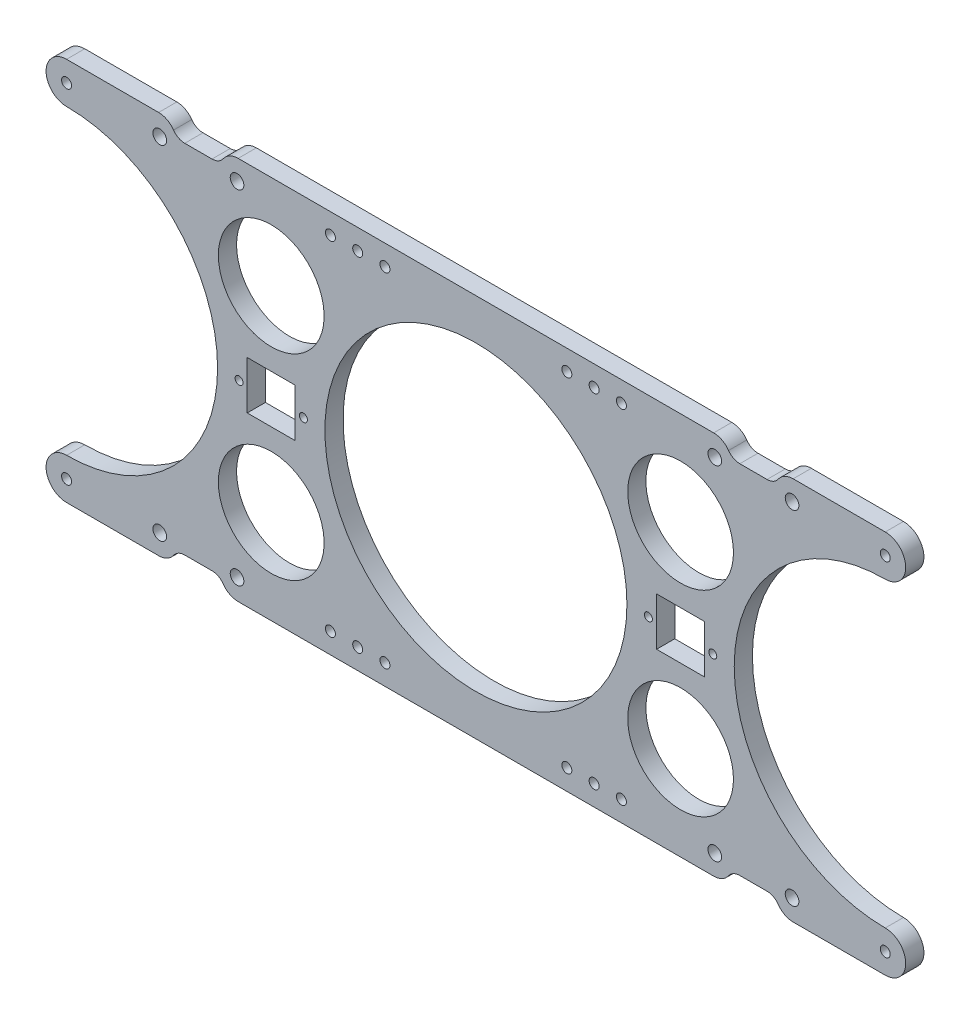
SolidWorks part; units mm, degrees
material "1060 Alloy"
ref_plane "Front Plane" through (0, 0, 0) normal (0, 0, 1) x (1, 0, 0)
ref_plane "Top Plane" through (0, 0, 0) normal (0, 1, 0) x (1, 0, 0)
ref_plane "Right Plane" through (0, 0, 0) normal (1, 0, 0) x (0, 0, -1)
sketch "Sketch1" plane through (0, 0, 0) normal (0, 0, 1) x (1, 0, 0)
  line L0 (0, 0) -> (225.1042, 0) construction
  line L1 (112.5521, -53.975) -> (112.5521, 53.975) construction
  line L2 (0, 83.05) -> (225.1042, 83.05) construction
  line L3 (225.1042, 83.05) -> (225.1042, -83.05) construction
  line L4 (-225.1042, 105.55) -> (-167.6042, 105.55)
  line L5 (-225.1042, -105.55) -> (-167.6042, -105.55)
  line L6 (0, 83.05) -> (0, 0) construction
  line L7 (-99.3521, -13.2) -> (-99.3521, 13.2)
  line L8 (99.3521, -13.2) -> (125.7521, -13.2)
  line L9 (99.3521, -13.2) -> (99.3521, 13.2)
  line L10 (99.3521, 13.2) -> (125.7521, 13.2)
  line L11 (125.7521, -13.2) -> (125.7521, 13.2)
  line L12 (99.3521, -13.2) -> (125.7521, 13.2) construction
  line L13 (99.3521, 13.2) -> (125.7521, -13.2) construction
  line L14 (-99.3521, 13.2) -> (-125.7521, 13.2)
  line L15 (-125.7521, -13.2) -> (-125.7521, 13.2)
  line L16 (-99.3521, -13.2) -> (-125.7521, -13.2)
  line L17 (0, 83.05) -> (0, 98.05) construction
  line L18 (50, 94.3) -> (80, 94.3) construction
  line L19 (80, 94.3) -> (94.2894, 76.5986) construction
  line L20 (225.1042, 0) -> (148.4177, 105.55) construction
  line L21 (225.1042, 0) -> (148.4177, -105.55) construction
  line L38 (-236.3542, 105.55) -> (-236.3542, -105.55) construction
  line L39 (-236.3542, -105.55) -> (-167.6042, -105.55) construction
  line L40 (236.3542, -105.55) -> (236.3542, 105.55) construction
  line L41 (236.3542, 105.55) -> (167.6042, 105.55) construction
  line L42 (-160.1042, 98.05) -> (-145.1042, 98.05)
  line L44 (-152.6042, 98.05) -> (-152.6042, 105.55) construction
  line L45 (-137.6042, 105.55) -> (137.6042, 105.55)
  line L46 (-167.6042, 105.55) -> (-236.3542, 105.55) construction
  line L47 (-160.1042, -98.05) -> (-145.1042, -98.05)
  line L48 (160.1042, -98.05) -> (145.1042, -98.05)
  line L49 (160.1042, 98.05) -> (145.1042, 98.05)
  line L50 (-137.6042, -105.55) -> (137.6042, -105.55) construction
  line L51 (-137.6042, -105.55) -> (137.6042, -105.55)
  line L52 (167.6042, -105.55) -> (225.1042, -105.55)
  line L53 (167.6042, -105.55) -> (236.3542, -105.55) construction
  line L54 (137.6042, 105.55) -> (-137.6042, 105.55) construction
  line L55 (167.6042, 105.55) -> (225.1042, 105.55)
  circle A0 centre (0, 0) radius 83.05
  arc A1 (225.1042, 83.05) -> (225.1042, -83.05) centre (225.1042, 0) ccw
  circle A2 centre (112.5521, 53.975) radius 29.075
  circle A3 centre (112.5521, -53.975) radius 29.075
  arc A4 (225.1042, 83.05) -> (225.1042, 105.55) centre (225.1042, 94.3) ccw
  arc A5 (225.1042, -83.05) -> (225.1042, -105.55) centre (225.1042, -94.3) cw
  circle A6 centre (-112.5521, -53.975) radius 29.075
  arc A7 (-225.1042, -83.05) -> (-225.1042, -105.55) centre (-225.1042, -94.3) ccw
  arc A8 (-225.1042, 83.05) -> (-225.1042, 105.55) centre (-225.1042, 94.3) cw
  circle A9 centre (-112.5521, 53.975) radius 29.075
  arc A10 (-225.1042, 83.05) -> (-225.1042, -83.05) centre (-225.1042, 0) cw
  circle A11 centre (225.1042, 0) radius 94.3 construction
  circle A13 centre (-195.1042, 94.3) radius 2.75 construction
  circle A31 centre (94.8521, 0) radius 2.2
  circle A32 centre (130.2521, 0) radius 2.2
  circle A33 centre (-130.2521, 0) radius 2.2
  circle A34 centre (-94.8521, 0) radius 2.2
  circle A35 centre (130.2521, 0) radius 3.175 construction
  circle A36 centre (225.1042, 0) radius 88.9 construction
  arc A37 (-167.6042, 105.55) -> (-160.1042, 98.05) centre (-160.1042, 105.55) ccw
  arc A38 (-145.1042, 98.05) -> (-137.6042, 105.55) centre (-145.1042, 105.55) ccw
  circle A39 centre (-195.1042, 94.3) radius 7.5 construction
  circle A40 centre (-173.8542, 94.3) radius 3.75
  circle A42 centre (-131.3542, 94.3) radius 3.75
  arc A43 (-145.1042, -98.05) -> (-137.6042, -105.55) centre (-145.1042, -105.55) cw
  arc A44 (-167.6042, -105.55) -> (-160.1042, -98.05) centre (-160.1042, -105.55) cw
  circle A45 centre (-131.3542, -94.3) radius 3.75
  circle A46 centre (-173.8542, -94.3) radius 3.75
  circle A47 centre (131.3542, -94.3) radius 3.75
  arc A48 (145.1042, -98.05) -> (137.6042, -105.55) centre (145.1042, -105.55) ccw
  arc A49 (167.6042, -105.55) -> (160.1042, -98.05) centre (160.1042, -105.55) ccw
  circle A50 centre (173.8542, -94.3) radius 3.75
  circle A51 centre (131.3542, 94.3) radius 3.75
  arc A52 (145.1042, 98.05) -> (137.6042, 105.55) centre (145.1042, 105.55) cw
  arc A53 (167.6042, 105.55) -> (160.1042, 98.05) centre (160.1042, 105.55) cw
  circle A54 centre (173.8542, 94.3) radius 3.75
  point P9 (112.5521, 0)
  point P10 (112.5521, 0)
  point P24 (0, -98.05)
  point P25 (0, 98.05)
  point P30 (112.5521, 0)
  point P31 (225.1042, 94.3)
  point P32 (225.1042, -94.3)
  point P33 (-225.1042, -94.3)
  point P34 (-225.1042, 94.3)
  point P46 (65, 94.3)
  point P48 (-80, 94.3)
  point P49 (-65, 94.3)
  point P50 (50, 94.3)
  point P51 (80, 94.3)
  point P52 (-50, 94.3)
  point P54 (80, -94.3)
  point P55 (65, -94.3)
  point P56 (50, -94.3)
  point P57 (-50, -94.3)
  point P58 (-65, -94.3)
  point P59 (-80, -94.3)
  point P63 (195.1042, -94.3)
  point P66 (-195.1042, -94.3)
  point P67 (-195.1042, 94.3)
  point P70 (195.1042, 94.3)
  point P77 (0, 0)
  point P82 (0, 0)
  dimension "D1" = 166.1
  dimension "D3" = 58.15
  dimension "D10" = 5.5
  dimension "D16" = 4.4
  dimension "D20" = 6.35
  dimension "D21" = 177.8
  dimension "D11" = 7.5
  dimension "D14" = 15
  dimension "D13" = 7.5
  dimension "D2" = 12.7
  dimension "D4" = 22.5
  dimension "D5" = 26.4
  dimension "D7" = 50
  dimension "D6" = 15
  dimension "D8" = 36
  dimension "D17" = 4.5
  dimension "D18" = 211.1
  dimension "D19" = 472.7085
  dimension "D12" = 15
  dimension "D15" = 20
  dimension "D22" = 10
  dimension "D9" = 30
extrude "Boss-Extrude1" add sketch "Sketch1" along normal mid plane 10
sketch "Sketch2" plane through (0, 0, 0) normal (0, 1, 0) x (1, 0, 0)
  line L0 (-196.3542, 5) -> (-196.3542, -5) construction
  line L2 (-167.6042, 5) -> (-225.1042, 5) construction
  line L3 (-167.6042, -5) -> (-225.1042, -5) construction
  line L4 (0, 0) -> (110.0348, 0) construction
  line L5 (110.0348, 5) -> (110.0348, -5) construction
hole_wizard "M5 Clearance Hole1" positions "Sketch3" profile "Sketch4" hole size "M5" standard "ANSI Metric" end condition through all
sketch "Sketch3" plane through (0, 0, 5) normal (0, 0, 1) x (1, 0, 0)
  line L0 (-3000, 0) -> (3000, 0) construction
  line L1 (0, -1000) -> (0, 49000) construction
  point P0 (-80, 94.3)
  point P3 (-65, 94.3)
  point P6 (-50, 94.3)
  point P9 (50, 94.3)
  point P12 (65, 94.3)
  point P15 (80, 94.3)
  point P18 (-80, -94.3)
  point P21 (-65, -94.3)
  point P24 (-50, -94.3)
  point P27 (50, -94.3)
  point P30 (65, -94.3)
  point P33 (80, -94.3)
  point P78 (0, 0)
  point P96 (-225.1042, 94.3)
  point P105 (225.1042, 94.3)
  point P108 (225.1042, -94.3)
  point P111 (-225.1042, -94.3)
sketch "Sketch4" plane through (-80, 94.3, 5) normal (1, 0, 0) x (0, -1, 0)
  line L0 (0, 0) -> (0, 10)
  line L1 (0, 10) -> (2.75, 10)
  line L2 (2.75, 10) -> (2.75, 0)
  line L5 (2.75, 0) -> (0, 0)
  line L11 (0, -6.35) -> (0, 107.95) construction
  dimension "Thru Hole Dia." = 5.5
  dimension "Thru Hole Depth" = 10
fillet "Fillet1" radius 10 8 edges at (167.6042, 105.55, 0) (137.6042, 105.55, 0) (167.6042, -105.55, 0) (137.6042, -105.55, 0) (-137.6042, -105.55, 0) (-167.6042, -105.55, 0) (-137.6042, 105.55, 0) (-167.6042, 105.55, 0)
equation "\"D1@Sketch1\"=152.40 + (6.35*2) + 1"
